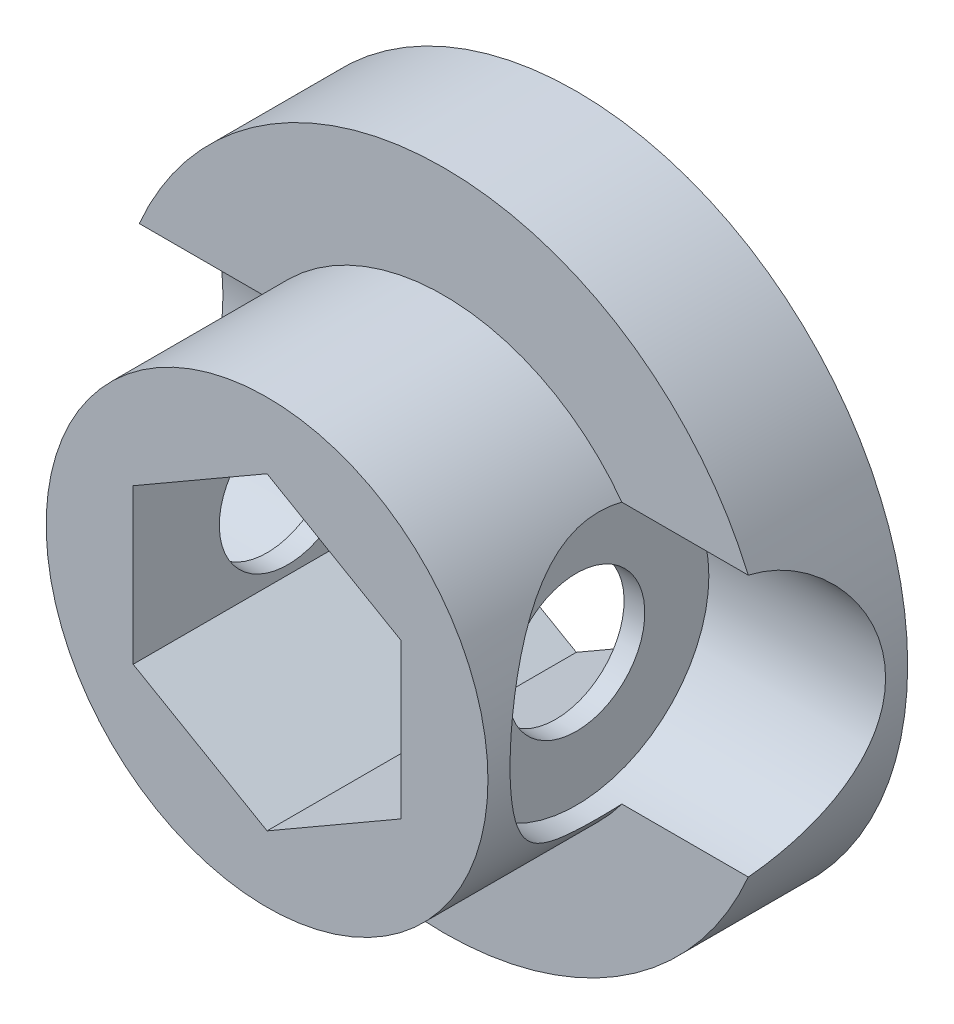
SolidWorks part; units mm, degrees
ref_plane "Front Plane" through (0, 0, 0) normal (0, 0, 1) x (1, 0, 0)
ref_plane "Top Plane" through (0, 0, 0) normal (0, 1, 0) x (1, 0, 0)
ref_plane "Right Plane" through (0, 0, 0) normal (1, 0, 0) x (0, 0, -1)
sketch "Sketch1" plane through (0, 0, 0) normal (0, 0, 1) x (1, 0, 0)
  line L2 (-3.0311, 1.75) -> (0, 3.5)
  line L3 (0, 3.5) -> (3.0311, 1.75)
  line L4 (3.0311, 1.75) -> (3.0311, -1.75)
  line L5 (3.0311, -1.75) -> (0, -3.5)
  line L6 (0, -3.5) -> (-3.0311, -1.75)
  line L7 (-3.0311, -1.75) -> (-3.0311, 1.75)
  circle A0 centre (0, 0) radius 5
  point P7 (0, 0)
  point P10 (0, 0)
extrude "Boss-Extrude2" add sketch "Sketch1" along normal blind 7
ref_plane "Plane1" through (0, 0, 0) normal (-1, 0, 0) x (0, 0, 1)
sketch "Sketch3" plane through (0, 0, 0) normal (0, 0, 1) x (1, 0, 0)
  circle A0 centre (0, 0) radius 7.5
  circle A1 centre (0, 0) radius 5
extrude "Boss-Extrude3" add sketch "Sketch3" along normal blind 3
sketch "Sketch2" plane through (0, 0, 0) normal (-1, 0, 0) x (0, 0, 1)
  line L0 (0, 0) -> (7, 0) construction
  line L1 (7, -5) -> (7, 5) construction
  circle A0 centre (3.5, 0) radius 1.55
extrude "Cut-Extrude1" cut sketch "Sketch2" against normal blind 5 and the other way blind 5
ref_plane "Plane2" through (-3.5, 0, 0) normal (-1, 0, 0) x (0, 0, 1)
ref_plane "Plane3" through (3.5, 0, 0) normal (-1, 0, 0) x (0, 0, 1)
sketch "Sketch4" plane through (-3.5, 0, 0) normal (-1, 0, 0) x (0, 0, 1)
  circle A0 centre (3.5, 0) radius 3
extrude "Cut-Extrude2" cut sketch "Sketch4" along normal blind 4
sketch "Sketch5" plane through (3.5, 0, 0) normal (-1, 0, 0) x (0, 0, 1)
  circle A0 centre (3.5, 0) radius 3
extrude "Cut-Extrude3" cut sketch "Sketch5" against normal blind 4
